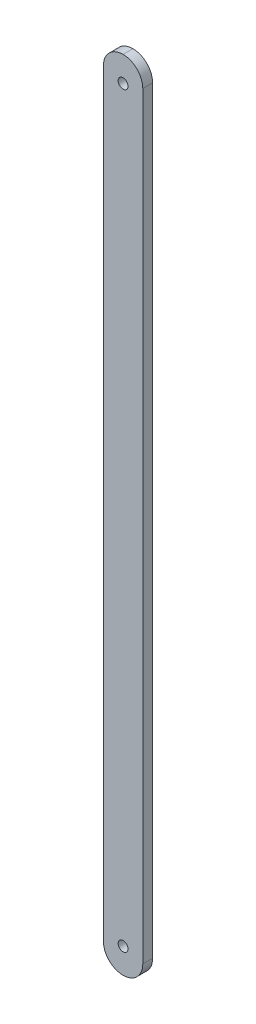
SolidWorks part; units mm, degrees
material "Acrylic (Medium-high impact)"
ref_plane "Front Plane" through (0, 0, 0) normal (0, 0, 1) x (1, 0, 0)
ref_plane "Top Plane" through (0, 0, 0) normal (0, 1, 0) x (1, 0, 0)
ref_plane "Right Plane" through (0, 0, 0) normal (1, 0, 0) x (0, 0, -1)
sketch "Sketch1" plane through (0, 0, 0) normal (0, 0, 1) x (1, 0, 0)
  line L1 (-25.4, 257.175) -> (0, 257.175)
  line L2 (-25.4, 257.175) -> (-25.4, -257.175)
  line L3 (-25.4, -257.175) -> (0, -257.175)
  line L4 (0, 257.175) -> (0, -257.175)
  point P5 (0, 0)
  dimension "D1" = 514.35
  dimension "D2" = 25.4
extrude "Boss-Extrude1" add sketch "Sketch1" along normal blind 6.35
fillet "Fillet1" radius 12.7 2 edges at (-25.4, 257.175, 3.175) (0, 257.175, 3.175)
fillet "Fillet2" radius 12.7 2 edges at (-25.4, -257.175, 3.175) (0, -257.175, 3.175)
sketch "Sketch2" plane through (0, 0, 6.35) normal (0, 0, 1) x (1, 0, 0)
  line L0 (0, -244.475) -> (0, 244.475) construction
  circle A0 centre (-12.7, 240.919) radius 3.175
  circle A1 centre (-12.7, -240.919) radius 3.175
  point P4 (0, 0)
  dimension "D2" = 6.35
  dimension "D3" = 6.35
  dimension "D4" = 481.838
  dimension "D5" = 240.919
  dimension "D1" = 12.7
extrude "Cut-Extrude1" cut sketch "Sketch2" against normal through all
